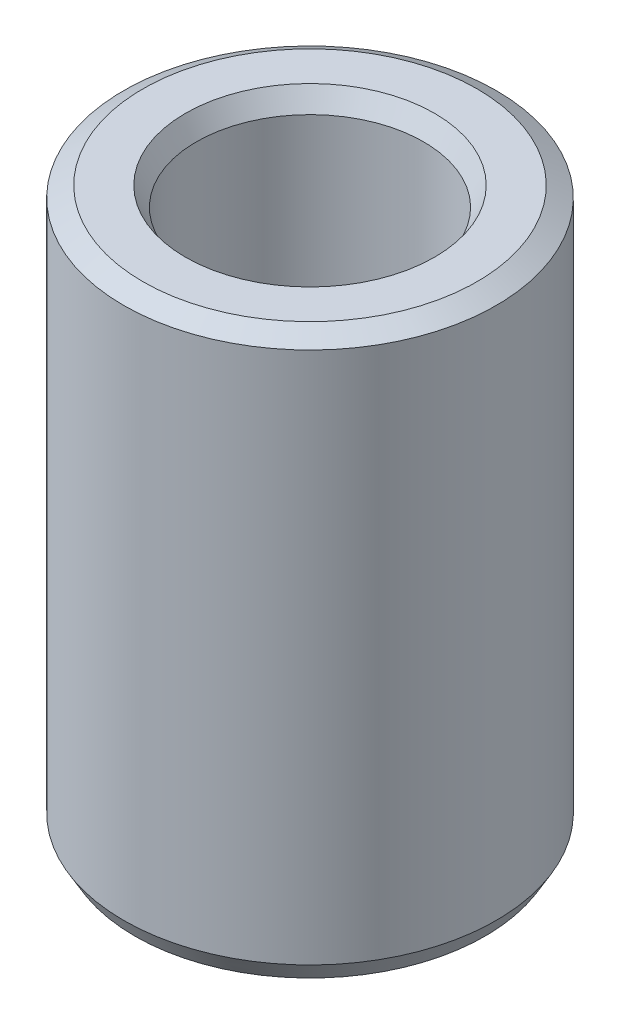
SolidWorks part; units mm, degrees
ref_plane "Front Plane" through (0, 0, 0) normal (0, 0, 1) x (1, 0, 0)
ref_plane "Top Plane" through (0, 0, 0) normal (0, 1, 0) x (1, 0, 0)
ref_plane "Right Plane" through (0, 0, 0) normal (1, 0, 0) x (0, 0, -1)
sketch "Sketch1" plane through (0, 0, 0) normal (0, 1, 0) x (1, 0, 0)
  circle A0 centre (0, 0) radius 52.5
  dimension "SLEEVE_OD" = 105
extrude "Boss-Extrude1" add sketch "Sketch1" along normal blind 158.6693
sketch "Sketch2" plane through (0, 0, 0) normal (0, 1, 0) x (1, 0, 0)
  circle A0 centre (0, 0) radius 32.0245
  dimension "BORE_D" = 64.0489
extrude "Cut-Extrude1" cut sketch "Sketch2" along normal through all
chamfer "Chamfer1" distance 3.1125 angle 60 4 edges at (0, 158.6693, 32.0245) (0, 0, 32.0245) (0, 0, 52.5) (0, 158.6693, 52.5) first distance on face at (0, 158.6693, 32.0245) first distance on face at (0, 0, 32.0245) first distance on face at (0, 158.6693, 52.5)
